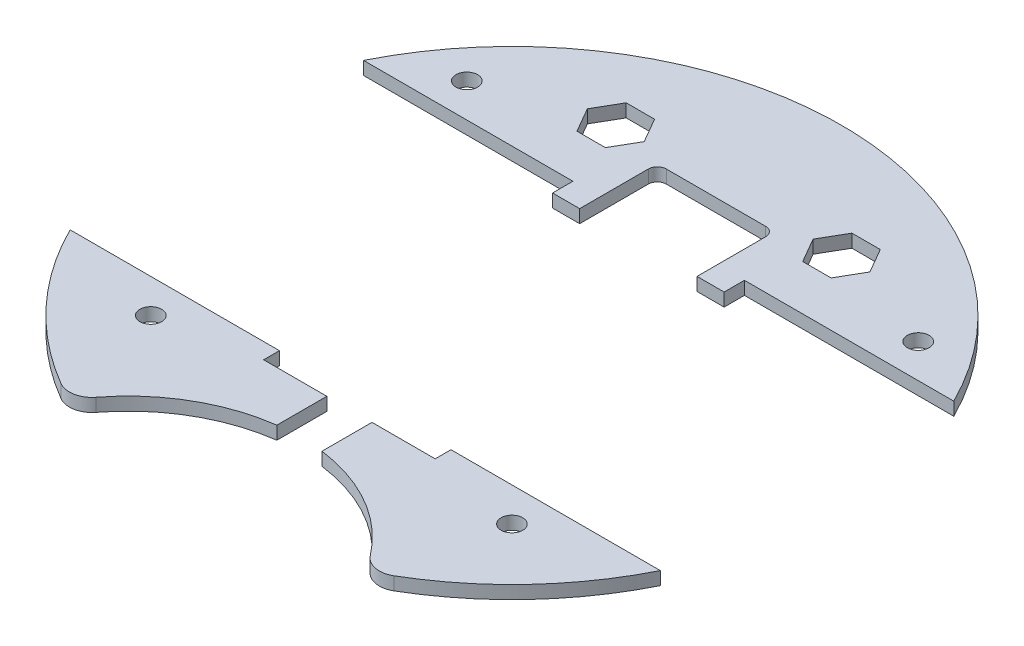
SolidWorks part; units mm, degrees
material "Acrylic (Medium-high impact)"
ref_plane "Front Plane" through (0, 0, 0) normal (0, 0, 1) x (1, 0, 0)
ref_plane "Top Plane" through (0, 0, 0) normal (0, 1, 0) x (1, 0, 0)
ref_plane "Right Plane" through (0, 0, 0) normal (1, 0, 0) x (0, 0, -1)
sketch "Sketch1" plane through (0, 0, 0) normal (0, 1, 0) x (1, 0, 0)
  line L0 (0, -85) -> (-32.7511, -65.2408) construction
  line L1 (0, -85) -> (0, 0) construction
  arc A0 (36.8566, -63.0126) -> (-36.8566, -63.0126) centre (0, 0) ccw
  arc A1 (30.3631, -61.7375) -> (-30.3631, -61.7375) centre (0, -85) ccw
  arc A2 (36.8566, -63.0126) -> (30.3631, -61.7375) centre (34.3322, -58.6967) cw
  arc A3 (-30.3631, -61.7375) -> (-36.8566, -63.0126) centre (-34.3322, -58.6967) cw
  dimension "D1" = 146
  dimension "D2" = 76.5
  dimension "D4" = 5
  dimension "D3" = 85
extrude "Boss-Extrude1" add sketch "Sketch1" along normal blind 2.9
sketch "solenoid placement" plane through (0, 2.9, 0) normal (0, 1, 0) x (1, 0, 0)
  line L4 (-19, -36) -> (19, -36)
  line L5 (-19, 28) -> (-19, -36)
  line L6 (19, 28) -> (-19, 28)
  line L7 (19, -36) -> (19, 28)
  line L8 (-19, -36) -> (19, -36)
  line L9 (-19, 28) -> (-19, -36)
  line L10 (19, 28) -> (-19, 28)
  line L11 (19, -36) -> (19, 28)
  dimension "D1" = 0
extrude "Cut-Extrude1" cut sketch "solenoid placement" against normal through all
sketch "Sketch4" plane through (0, 2.9, 0) normal (0, 1, 0) x (1, 0, 0)
  line L6 (-13, 28) -> (13, 28)
  line L7 (13, 28) -> (13, 43.2)
  line L8 (11, 45.2) -> (-11, 45.2)
  line L9 (-13, 43.2) -> (-13, 28)
  line L10 (-13, 28) -> (13, 28)
  line L11 (13, 28) -> (13, 43.2)
  line L12 (11, 45.2) -> (-11, 45.2)
  line L13 (-13, 43.2) -> (-13, 28)
  arc A4 (13, 43.2) -> (11, 45.2) centre (11, 43.2) ccw
  arc A5 (13, 43.2) -> (11, 45.2) centre (11, 43.2) ccw
  arc A6 (-11, 45.2) -> (-13, 43.2) centre (-11, 43.2) ccw
  arc A7 (-11, 45.2) -> (-13, 43.2) centre (-11, 43.2) ccw
  dimension "D1" = 0
extrude "Cut-Extrude4" cut sketch "Sketch4" against normal through all
sketch "Sketch5" plane through (0, 2.9, 0) normal (0, 1, 0) x (1, 0, 0)
  line L6 (-18.7069, 48) -> (-21.8534, 53.45)
  line L7 (-21.8534, 53.45) -> (-28.1466, 53.45)
  line L8 (-28.1466, 53.45) -> (-31.2931, 48)
  line L9 (-31.2931, 48) -> (-28.1466, 42.55)
  line L10 (-28.1466, 42.55) -> (-21.8534, 42.55)
  line L11 (-21.8534, 42.55) -> (-18.7069, 48)
  line L12 (-18.7069, 48) -> (-21.8534, 53.45)
  line L13 (-21.8534, 53.45) -> (-28.1466, 53.45)
  line L14 (-28.1466, 53.45) -> (-31.2931, 48)
  line L15 (-31.2931, 48) -> (-28.1466, 42.55)
  line L16 (-28.1466, 42.55) -> (-21.8534, 42.55)
  line L17 (-21.8534, 42.55) -> (-18.7069, 48)
  line L18 (18.7069, 48) -> (21.8534, 42.55)
  line L19 (21.8534, 53.45) -> (18.7069, 48)
  line L20 (28.1466, 53.45) -> (21.8534, 53.45)
  line L21 (31.2931, 48) -> (28.1466, 53.45)
  line L22 (28.1466, 42.55) -> (31.2931, 48)
  line L23 (21.8534, 42.55) -> (28.1466, 42.55)
  line L24 (18.7069, 48) -> (21.8534, 42.55)
  line L25 (21.8534, 53.45) -> (18.7069, 48)
  line L26 (28.1466, 53.45) -> (21.8534, 53.45)
  line L27 (31.2931, 48) -> (28.1466, 53.45)
  line L28 (28.1466, 42.55) -> (31.2931, 48)
  line L29 (21.8534, 42.55) -> (28.1466, 42.55)
  dimension "D1" = 0
  dimension "D2" = 0
extrude "Cut-Extrude5" cut sketch "Sketch5" against normal through all
sketch "Sketch6" plane through (0, 2.9, 0) normal (0, 1, 0) x (1, 0, 0)
  circle A1 centre (40, -40) radius 2.4
  circle A2 centre (40, -40) radius 2.4
  circle A3 centre (-40, -40) radius 2.4
  circle A4 centre (-40, -40) radius 2.4
  circle A5 centre (-50, 40) radius 2.4
  circle A6 centre (-50, 40) radius 2.4
  circle A7 centre (50, 40) radius 2.4
  circle A8 centre (50, 40) radius 2.4
  dimension "D1" = 0
  dimension "D2" = 0
  dimension "D3" = 0
  dimension "D4" = 0
extrude "Cut-Extrude6" cut sketch "Sketch6" against normal through all
sketch "Sketch3" plane through (0, 2.9, 0) normal (0, 1, 0) x (1, 0, 0)
  line L0 (-19, 28) -> (-19, 32.5)
  line L1 (73, -32.5) -> (-73, -32.5)
  line L2 (73, -32.5) -> (73, 32.5)
  line L3 (73, 32.5) -> (19, 32.5)
  line L4 (-73, -32.5) -> (-73, 32.5)
  line L5 (73, -32.5) -> (-73, 32.5) construction
  line L6 (73, 32.5) -> (-73, -32.5) construction
  line L7 (-19, 28) -> (19, 28)
  line L8 (19, 28) -> (19, 32.5)
  line L9 (-19, 32.5) -> (-73, 32.5)
  arc A0 (36.8566, -63.0126) -> (-36.8566, -63.0126) centre (0, 0) ccw construction
  point P0 (0, 0)
  dimension "D1" = 65
extrude "Cut-Extrude3" cut sketch "Sketch3" against normal through all
sketch "Sketch7" plane through (0, 2.9, 0) normal (0, 1, 0) x (1, 0, 0)
  line L4 (5, 0) -> (-5, 0)
  line L5 (5, -62.8025) -> (5, 0)
  line L6 (-5, -62.8025) -> (5, -62.8025)
  line L7 (-5, 0) -> (-5, -62.8025)
  line L8 (5, 0) -> (-5, 0)
  line L9 (5, -62.8025) -> (5, 0)
  line L10 (-5, -62.8025) -> (5, -62.8025)
  line L11 (-5, 0) -> (-5, -62.8025)
  dimension "D1" = 0
extrude "Cut-Extrude7" cut sketch "Sketch7" against normal through all
equation "\"smallPulleyTeeth\"= 15"
equation "\"largePulleyTeeth\"= 30"
equation "\"eighthThick\"= 2.9mm"
equation "\"sixteenthThick\" = 1.7mm"
equation "\"quarterThick\"=6.0mm"
equation "\"OD\" = 146mm"
equation "\"puckAngle\" = 60.5deg"
equation "\"D1@Sketch1\"=\"OD\""
equation "\"puckDiam\" = 76.5mm"
equation "\"D2@Sketch1\"=\"puckDiam\""
equation "\"D1@Boss-Extrude1\"=\"eighthThick\""
equation "\"axlePress\" = 5.9mm"
equation "\"press\" = 0.2mm"
equation "\"wheelClear\" = 0.3mm"
equation "\"10-32clear\" = 4.8mm"
equation "\"6-32clear\" = 3.3mm"
equation "\"8-32clear\" = 4.0mm"
equation "\"wheelHeight\" = 22mm"
equation "\"wheelWell\" = 65mm"
equation "\"D1@Sketch3\"=\"wheelWell\""
equation "\"puckDist\" = 85mm"
equation "\"scoopFillet\" = 5mm"
equation "\"4-40clear\" = 3.0mm"
equation "\"D3@Sketch1\"=\"puckDist\""
equation "\"D4@Sketch1\"=\"scoopFillet\""
